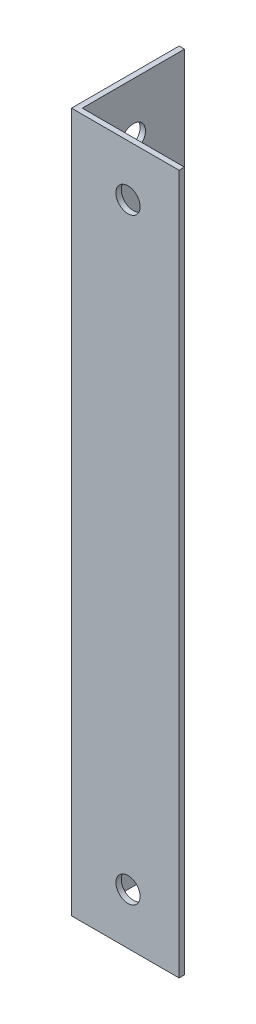
SolidWorks part; units mm, degrees
material "1060 Сплав"
ref_plane "Спереди" through (0, 0, 0) normal (0, 0, 1) x (1, 0, 0)
ref_plane "Сверху" through (0, 0, 0) normal (0, 1, 0) x (1, 0, 0)
ref_plane "Справа" through (0, 0, 0) normal (1, 0, 0) x (0, 0, -1)
sketch "Эскиз1" plane through (0, 0, 0) normal (0, 1, 0) x (1, 0, 0)
  line L0 (0, 0) -> (0, 20)
  line L1 (0, 20) -> (1, 20)
  line L2 (1, 20) -> (1, 1)
  line L3 (1, 1) -> (20, 1)
  line L4 (20, 1) -> (20, 0)
  line L5 (20, 0) -> (0, 0)
  dimension "D1" = 1
  dimension "D2" = 20
extrude "Бобышка-Вытянуть1" add sketch "Эскиз1" along normal blind 130
sketch "Эскиз2" plane through (0, 0, -1) normal (0, 0, -1) x (-1, 0, 0)
  line L0 (-10.5, 0) -> (-10.5, 9.5) construction
  line L1 (-20, 0) -> (-1, 0) construction
  circle A0 centre (-10.5, 9.5) radius 2.25
  dimension "D2" = 4.5
  dimension "D1" = 9.5
extrude "Вырез-Вытянуть1" cut sketch "Эскиз2" against normal through all
sketch "Эскиз3" plane through (0, 0, 0) normal (-1, 0, 0) x (0, 0, 1)
  circle A0 centre (-10.5, 13.5) radius 2.25 construction
  circle A1 centre (-10.5, 13.5) radius 2.25
  circle A2 centre (-10.5, 120.5) radius 2.25 construction
  circle A3 centre (-10.5, 120.5) radius 2.25
extrude "Вырез-Вытянуть2" cut sketch "Эскиз3" against normal through all
sketch "Эскиз4" plane through (0, 0, -1) normal (0, 0, -1) x (-1, 0, 0)
  line L0 (-10.5, 130) -> (-10.5, 120.5) construction
  line L1 (-20, 130) -> (-1, 130) construction
  circle A0 centre (-10.5, 120.5) radius 2.25
  dimension "D2" = 4.5
  dimension "D1" = 9.5
extrude "Вырез-Вытянуть3" cut sketch "Эскиз4" against normal through all
